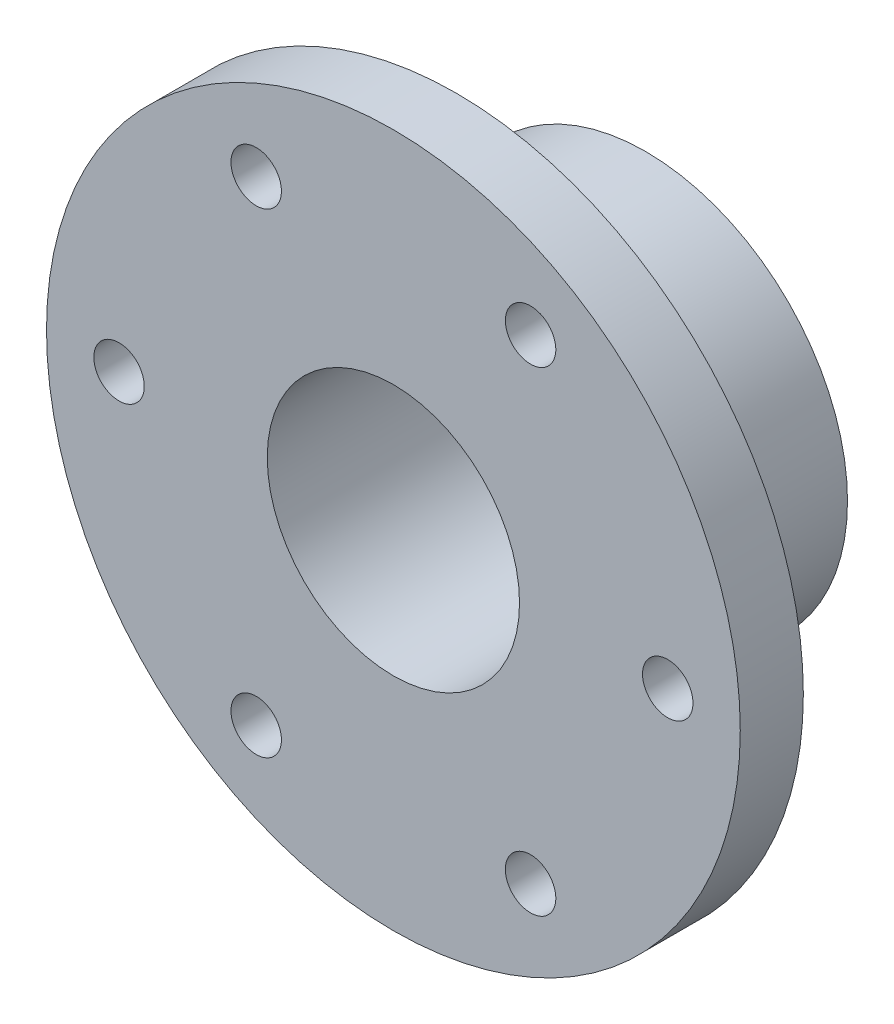
SolidWorks part; units mm, degrees
material "1060 Сплав"
ref_plane "Спереди" through (0, 0, 0) normal (0, 0, 1) x (1, 0, 0)
ref_plane "Сверху" through (0, 0, 0) normal (0, 1, 0) x (1, 0, 0)
ref_plane "Справа" through (0, 0, 0) normal (1, 0, 0) x (0, 0, -1)
sketch "Эскиз1" plane through (0, 0, 0) normal (0, 0, 1) x (1, 0, 0)
  circle A1 centre (0, 0) radius 27.5
  dimension "D2" = 55
extrude "Бобышка-Вытянуть1" add sketch "Эскиз1" along normal blind 5
sketch "Эскиз2" plane through (0, 0, 0) normal (0, 0, -1) x (-1, 0, 0)
  circle A0 centre (0, 0) radius 16
  circle A2 centre (0, 0) radius 10
  dimension "D1" = 32
  dimension "D2" = 20
extrude "Вырез-Вытянуть2" cut sketch "Эскиз2" against normal through all contours A2
extrude "Бобышка-Вытянуть9" add sketch "Эскиз2<12>" along normal blind 15
sketch "Эскиз2<12>" plane through (0, 0, 0) normal (0, 0, -1) x (-1, 0, 0) same geometry as "Эскиз2"
sketch "Эскиз12" plane through (0, 0, 0) normal (0, 0, -1) x (-1, 0, 0)
  line L0 (0, 0) -> (-21.75, 0) construction
  circle A0 centre (0, 0) radius 21.75 construction
  circle A1 centre (-21.75, 0) radius 2
  circle A2 centre (0, 0) radius 21.75 construction
  circle A3 centre (-10.875, 18.8361) radius 2
  circle A4 centre (0, 0) radius 21.75 construction
  circle A5 centre (10.875, 18.8361) radius 2
  circle A6 centre (0, 0) radius 21.75 construction
  circle A7 centre (21.75, 0) radius 2
  circle A8 centre (0, 0) radius 21.75 construction
  circle A9 centre (10.875, -18.8361) radius 2
  circle A10 centre (0, 0) radius 21.75 construction
  circle A11 centre (-10.875, -18.8361) radius 2
  dimension "D1" = 43.5
  dimension "D2" = 4
  dimension "D3" = 6
extrude "Вырез-Вытянуть3" cut sketch "Эскиз12" against normal through all contours A7 | A5 | A3 | A1 | A11 | A9
chamfer "Фаска1" distance 0.5 angle 45 6 edges at (-23.75, 0, 0) (-12.875, -18.8361, 0) (8.875, -18.8361, 0) (19.75, 0, 0) (-12.875, 18.8361, 0) (8.875, 18.8361, 0)
